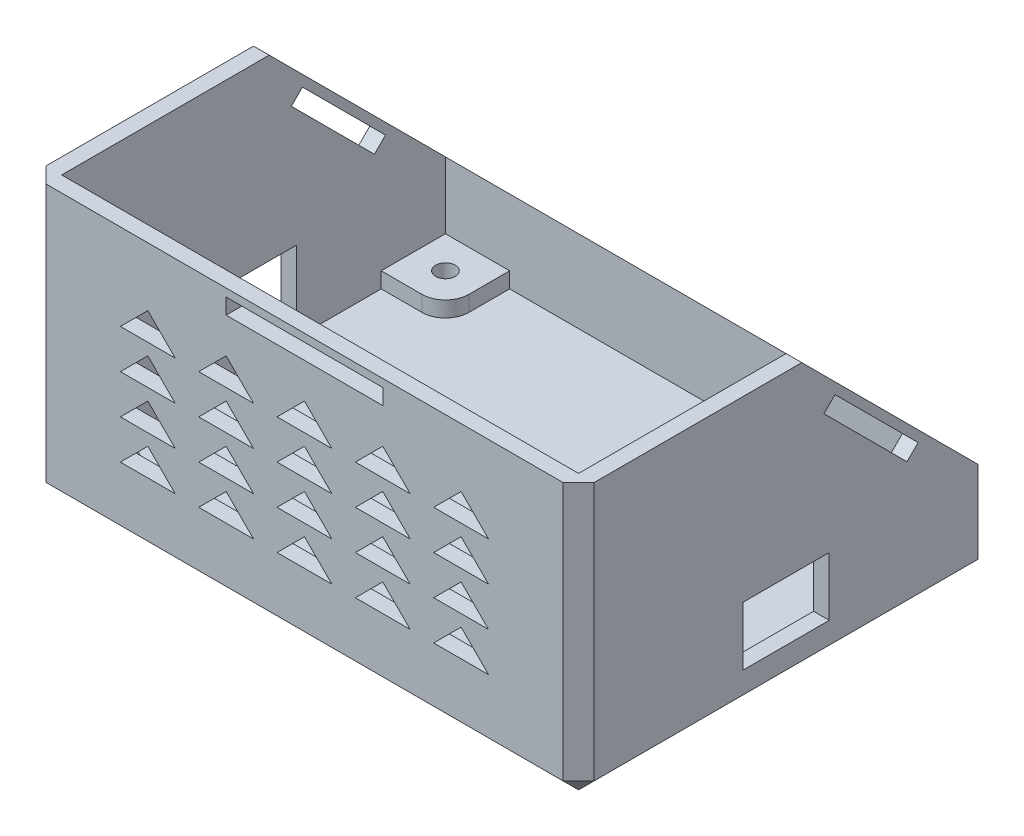
SolidWorks part; units mm, degrees
ref_plane "Front" through (0, 0, 0) normal (0, 0, 1) x (1, 0, 0)
ref_plane "Top" through (0, 0, 0) normal (0, 1, 0) x (1, 0, 0)
ref_plane "Right" through (0, 0, 0) normal (1, 0, 0) x (0, 0, -1)
sketch "Sketch1" plane through (0, 0, 0) normal (0, 1, 0) x (1, 0, 0)
  line L0 (-35, 26.5) -> (35, 26.5)
  line L1 (-33, -24.5) -> (33, -24.5)
  line L2 (-33, -24.5) -> (-33, 24.5)
  line L3 (-33, 24.5) -> (33, 24.5)
  line L4 (33, -24.5) -> (33, 24.5)
  line L5 (-33, -24.5) -> (33, 24.5) construction
  line L6 (-33, 24.5) -> (33, -24.5) construction
  line L7 (35, -26.5) -> (35, 26.5)
  line L8 (-35, -26.5) -> (35, -26.5)
  line L9 (-35, -26.5) -> (-35, 26.5)
  point P0 (0, 0)
  dimension "D1" = 49
  dimension "D2" = 66
  dimension "D3" = 2
extrude "Boss-Extrude1" add sketch "Sketch1" along normal blind 2 contours L1 L4 L3 L2 | L9 L8 L7 L0 L4 L1 L2 L3 region at (0, 0, -25.622) region at (0, 0, 0)
extrude "Boss-Extrude2" add sketch "Sketch1<3>" along normal blind 33 from surface starting at face at (0, 2, 0)
sketch "Sketch1<3>" plane through (0, 0, 0) normal (0, 1, 0) x (1, 0, 0) same geometry as "Sketch1"
chamfer "Chamfer1" distance 2 angle 45 8 edges at (0, 0, 26.5) (35, 17.5, 26.5) (35, 0, 0) (35, 17.5, -26.5) (0, 0, -26.5) (-35, 17.5, -26.5) (-35, 0, 0) (-35, 17.5, 26.5)
sketch "Sketch2" plane through (0, 2, 0) normal (0, 1, 0) x (1, 0, 0)
  line L0 (-33, 16.3) -> (-27.8, 16.3)
  line L1 (-33, 24.5) -> (-24.8, 24.5)
  line L2 (-33, 24.5) -> (-33, 16.3)
  line L3 (-33, 16.3) -> (-24.8, 16.3) construction
  line L4 (-24.8, 24.5) -> (-24.8, 16.3) construction
  line L5 (-24.8, 24.5) -> (-24.8, 19.3)
  line L7 (-28.9, -20.4) -> (28.9, -20.4) construction
  line L8 (-28.9, -20.4) -> (-28.9, 20.4) construction
  line L9 (-28.9, 20.4) -> (28.9, 20.4) construction
  line L10 (28.9, -20.4) -> (28.9, 20.4) construction
  line L11 (-28.9, -20.4) -> (28.9, 20.4) construction
  line L12 (-28.9, 20.4) -> (28.9, -20.4) construction
  circle A0 centre (-28.9, 20.4) radius 1.25
  arc A1 (-27.8, 16.3) -> (-24.8, 19.3) centre (-27.8, 19.3) ccw
  point P7 (0, 0)
  point P8 (-24.8, 20.4)
  point P10 (-28.9, 16.3)
  point P13 (-24.8, 16.3)
  dimension "D1" = 3
  dimension "D3" = 2.5
  dimension "D2" = 40.8
extrude "Boss-Extrude3" add sketch "Sketch2" along normal blind 2
mirror "Mirror1" about plane through (0, 0, 0) normal (0, 0, 1) of "Boss-Extrude3"
mirror "Mirror2" about plane through (0, 0, 0) normal (1, 0, 0) of "Boss-Extrude3", "Mirror1"
sketch "Sketch3" plane through (0, 0, 0) normal (0, -1, 0) x (1, 0, 0)
  line L0 (-30.1124, 22.5) -> (-27.6876, 22.5)
  line L1 (-27.6876, 22.5) -> (-26.4751, 20.4)
  line L2 (-26.4751, 20.4) -> (-27.6876, 18.3)
  line L3 (-27.6876, 18.3) -> (-30.1124, 18.3)
  line L4 (-30.1124, 18.3) -> (-31.3249, 20.4)
  line L5 (-31.3249, 20.4) -> (-30.1124, 22.5)
  circle A1 centre (-28.9, 20.4) radius 2.4249 construction
  dimension "D1" = 4.2
extrude "Cut-Extrude1" cut sketch "Sketch3" against normal blind 1.6
mirror "Mirror3" about plane through (0, 0, 0) normal (0, 0, 1) of "Cut-Extrude1"
mirror "Mirror4" about plane through (0, 0, 0) normal (1, 0, 0) of "Mirror3", "Cut-Extrude1"
sketch "Sketch4" plane through (0, 2, 0) normal (0, 1, 0) x (1, 0, 0)
  circle A0 centre (28.9, -20.4) radius 1.25
  circle A1 centre (28.9, 20.4) radius 1.25
  circle A2 centre (-28.9, 20.4) radius 1.25
  circle A3 centre (-28.9, -20.4) radius 1.25
  circle A4 centre (-28.9, -20.4) radius 1.25 construction
extrude "Cut-Extrude2" cut sketch "Sketch4" against normal through all both and the other way through all
sketch "Sketch7" plane through (35, 0, 0) normal (1, 0, 0) x (0, 0, -1)
  line L1 (-5.5, 12.25) -> (5.5, 12.25)
  line L2 (-5.5, 12.25) -> (-5.5, 4.75)
  line L3 (-5.5, 4.75) -> (5.5, 4.75)
  line L4 (5.5, 12.25) -> (5.5, 4.75)
  point P4 (0, 4.75)
  dimension "D1" = 11
  dimension "D2" = 7.5
  dimension "D3" = 0.75
extrude "Cut-Extrude5" cut sketch "Sketch7" against normal through all
sketch "Sketch5" plane through (0, 0, 24.5) normal (0, 0, -1) x (-1, 0, 0)
  line L0 (33, 35) -> (-33, 35) construction
  line L1 (-10, 34) -> (10, 34)
  line L2 (-10, 34) -> (-10, 32)
  line L3 (-10, 32) -> (10, 32)
  line L4 (10, 34) -> (10, 32)
  point P4 (0, 34)
  dimension "D1" = 2
  dimension "D2" = 1
  dimension "D3" = 20
extrude "Cut-Extrude3" cut sketch "Sketch5" against normal through all both and the other way through all
sketch "Sketch8" plane through (35, 0, 0) normal (1, 0, 0) x (0, 0, -1)
  line L0 (-4.5, 35) -> (-4.5, 24)
  line L1 (24.5, 35) -> (-24.5, 35) construction
  line L2 (-4.5, 24) -> (10.5, 24)
  line L3 (10.5, 24) -> (10.5, 12.5486)
  line L4 (10.5, 12.5486) -> (26.5, 12.5486)
  line L5 (26.5, 35) -> (26.5, 2) construction
  line L6 (-4.5, 35) -> (26.5, 35)
  line L7 (26.5, 35) -> (26.5, 12.5486)
  line L8 (-24.5, 35) -> (-24.5, 2) construction
  dimension "D1" = 20
  dimension "D2" = 15
  dimension "D3" = 11
  dimension "D4" = 11.4514
extrude "Cut-Extrude7" [suppressed] cut sketch "Sketch8" against normal through all and the other way through all
sketch "Sketch9" plane through (35, 0, 0) normal (1, 0, 0) x (0, 0, -1)
  line L0 (2, 35) -> (26.5, 10.5)
  line L1 (24.5, 35) -> (-24.5, 35) construction
  line L3 (2, 35) -> (26.5, 35)
  line L4 (26.5, 35) -> (26.5, 10.5)
  line L5 (26.5, 35) -> (26.5, 2) construction
  dimension "D1" = 24.5
  dimension "D3" = 45
extrude "Cut-Extrude8" cut sketch "Sketch9" against normal through all
sketch "Sketch6" plane through (-33, 0, 0) normal (1, 0, 0) x (0, 0, -1)
  line L1 (6.2426, 29.3431) -> (16.8492, 18.7365)
  line L2 (6.2426, 29.3431) -> (4.8284, 27.9289)
  line L3 (4.8284, 27.9289) -> (15.435, 17.3223)
  line L4 (16.8492, 18.7365) -> (15.435, 17.3223)
  line L6 (2, 35) -> (24.5, 12.5) construction
  dimension "D1" = 15
  dimension "D2" = 2
  dimension "D3" = 1
  dimension "D4" = 7
extrude "Cut-Extrude4" cut sketch "Sketch6" against normal through all both and the other way through all
sketch "Sketch10" plane through (0, 0, 26.5) normal (0, 0, 1) x (1, 0, 0)
  line L0 (-28.2743, 28) -> (0, 28) construction
  line L1 (-28.2743, 28) -> (-28.2743, 26)
  line L2 (0, 28) -> (0, 26)
  line L3 (-28.2743, 26) -> (0, 26) construction
  spline S0 degree 4 poles (-28.5449, 27.7323) (-28.4703, 27.8051) (-28.3096, 27.9634) (-28.0891, 28.1885) (-27.7474, 28.5166) (-27.4578, 28.7408) (-27.1833, 28.8969) (-26.9792, 28.9694) (-26.7891, 29.0025) (-26.6154, 29.0023) (-26.4253, 28.969) (-26.2191, 28.8938) (-25.9523, 28.7444) (-25.6444, 28.5016) (-25.3138, 28.185) (-24.9517, 27.815) (-24.6211, 27.4984) (-24.3132, 27.2556) (-24.0464, 27.1062) (-23.8402, 27.031) (-23.6501, 26.9977) (-23.4764, 26.9975) (-23.2866, 27.0302) (-23.0803, 27.105) (-22.8134, 27.2536) (-22.5033, 27.4977) (-22.2688, 27.7226) (-21.9845, 28.0067) (-21.7217, 28.2692) (-21.4842, 28.4974) (-21.176, 28.7415) (-20.9066, 28.8936) (-20.6955, 28.97) (-20.5054, 29.0024) (-20.3321, 29.0022) (-20.1418, 28.969) (-19.9305, 28.8918) (-19.6613, 28.7391) (-19.3545, 28.4954) (-19.0269, 28.181) (-18.6722, 27.819) (-18.3446, 27.5046) (-18.0378, 27.2609) (-17.7686, 27.1082) (-17.5574, 27.031) (-17.3671, 26.9978) (-17.1937, 26.9976) (-17.0037, 27.03) (-16.7926, 27.1064) (-16.5231, 27.2585) (-16.2149, 27.5026) (-15.8864, 27.8183) (-15.5296, 28.1817) (-15.2011, 28.4974) (-14.8929, 28.7415) (-14.6234, 28.8936) (-14.4123, 28.97) (-14.2222, 29.0024) (-14.0489, 29.0022) (-13.8586, 28.969) (-13.6473, 28.8918) (-13.3781, 28.7391) (-13.0713, 28.4954) (-12.7437, 28.181) (-12.389, 27.819) (-12.0614, 27.5046) (-11.7546, 27.2609) (-11.4855, 27.1082) (-11.2742, 27.031) (-11.0839, 26.9978) (-10.9105, 26.9976) (-10.7205, 27.03) (-10.5094, 27.1064) (-10.2399, 27.2585) (-9.9317, 27.5026) (-9.6032, 27.8183) (-9.2464, 28.1817) (-8.9179, 28.4974) (-8.6097, 28.7415) (-8.3402, 28.8936) (-8.1291, 28.97) (-7.9391, 29.0024) (-7.7657, 29.0022) (-7.5754, 28.969) (-7.3641, 28.8918) (-7.0949, 28.7391) (-6.7881, 28.4954) (-6.4605, 28.181) (-6.1059, 27.819) (-5.7782, 27.5046) (-5.4715, 27.2609) (-5.2023, 27.1082) (-4.991, 27.031) (-4.8007, 26.9978) (-4.6273, 26.9976) (-4.4373, 27.03) (-4.2262, 27.1064) (-3.9567, 27.2585) (-3.6485, 27.5026) (-3.32, 27.8183) (-2.9632, 28.1817) (-2.6347, 28.4974) (-2.3265, 28.7415) (-2.057, 28.8936) (-1.8459, 28.97) (-1.6559, 29.0024) (-1.4825, 29.0022) (-1.2922, 28.969) (-1.0809, 28.8918) (-0.8117, 28.7391) (-0.505, 28.4954) (-0.1773, 28.181) (0.1773, 27.819) (0.505, 27.5046) (0.8117, 27.2609) (1.0809, 27.1082) (1.2922, 27.031) (1.4825, 26.9978) (1.6559, 26.9976) (1.8459, 27.03) (2.057, 27.1064) (2.3265, 27.2585) (2.6347, 27.5026) (2.9632, 27.8183) (3.32, 28.1817) (3.6485, 28.4974) (3.9567, 28.7415) (4.2262, 28.8936) (4.4373, 28.97) (4.6273, 29.0024) (4.8007, 29.0022) (4.991, 28.969) (5.2023, 28.8918) (5.4715, 28.7391) (5.7782, 28.4954) (6.1059, 28.181) (6.4605, 27.819) (6.7881, 27.5046) (7.0949, 27.2609) (7.3641, 27.1082) (7.5754, 27.031) (7.7657, 26.9978) (7.9391, 26.9976) (8.1291, 27.03) (8.3402, 27.1064) (8.6097, 27.2585) (8.9179, 27.5026) (9.2464, 27.8183) (9.6032, 28.1817) (9.9317, 28.4974) (10.2399, 28.7415) (10.5094, 28.8936) (10.7205, 28.97) (10.9105, 29.0024) (11.0839, 29.0022) (11.2742, 28.969) (11.4855, 28.8918) (11.7546, 28.7391) (12.0614, 28.4954) (12.389, 28.181) (12.7437, 27.819) (13.0713, 27.5046) (13.3781, 27.2609) (13.6473, 27.1082) (13.8586, 27.031) (14.0489, 26.9978) (14.2222, 26.9976) (14.4123, 27.03) (14.6234, 27.1064) (14.8929, 27.2585) (15.2011, 27.5026) (15.4388, 27.731) (15.6535, 27.946) (16.1642, 28.4542) (16.5088, 28.7676) (17.0389, 29.0097) (17.5058, 29.0109) (17.9194, 28.8311) (18.2971, 28.5403) (18.7576, 28.0983) (19.2008, 27.6407) (19.6509, 27.2313) (20.1778, 26.9912) (20.6495, 26.9884) (21.1777, 27.222) (21.7191, 27.7123) (22.2515, 28.2756) (22.7935, 28.7698) (23.3211, 29.0093) (23.7925, 29.011) (24.2049, 28.829) (24.5827, 28.5381) (24.9536, 28.1828) (25.301, 27.8281) (25.5956, 27.5448) (25.8423, 27.3416) (26.0345, 27.2133) (26.1568, 27.1427) (26.2955, 27.0788) (26.4442, 27.0275) (26.5772, 27.0044) (26.7085, 26.9975) (26.8225, 27.0051) (26.946, 27.0242) (27.0781, 27.0666) (27.1806, 27.1097) (27.2449, 27.1424) (27.2764, 27.1598) knots 0 0 0 0 0 0.005919 0.014015 0.02211 0.02645 0.030317 0.033015 0.035714 0.038403 0.041092 0.044998 0.049324 0.057392 0.06546 0.073527 0.081595 0.085922 0.089827 0.092516 0.095205 0.097904 0.100602 0.104469 0.108809 0.116905 0.125 0.125 0.133332 0.141664 0.146479 0.150644 0.153498 0.156276 0.159039 0.161939 0.166084 0.170918 0.179209 0.1875 0.195791 0.204082 0.208916 0.213061 0.215961 0.218724 0.221502 0.224356 0.228521 0.233336 0.241668 0.25 0.258332 0.266664 0.271479 0.275644 0.278498 0.281276 0.284039 0.286939 0.291084 0.295918 0.304209 0.3125 0.320791 0.329082 0.333916 0.338061 0.340961 0.343724 0.346502 0.349356 0.353521 0.358336 0.366668 0.375 0.383332 0.391664 0.396479 0.400644 0.403498 0.406276 0.409039 0.411939 0.416084 0.420918 0.429209 0.4375 0.445791 0.454082 0.458916 0.463061 0.465961 0.468724 0.471502 0.474356 0.478521 0.483336 0.491668 0.5 0.508332 0.516664 0.521479 0.525644 0.528498 0.531276 0.534039 0.536939 0.541084 0.545918 0.554209 0.5625 0.570791 0.579082 0.583916 0.588061 0.590961 0.593724 0.596502 0.599356 0.603521 0.608336 0.616668 0.625 0.633332 0.641664 0.646479 0.650644 0.653498 0.656276 0.659039 0.661939 0.666084 0.670918 0.679209 0.6875 0.695791 0.704082 0.708916 0.713061 0.715961 0.718724 0.721502 0.724356 0.728521 0.733336 0.741668 0.75 0.758332 0.766664 0.771479 0.775644 0.778498 0.781276 0.784039 0.786939 0.791084 0.795918 0.804209 0.8125 0.820791 0.829082 0.833916 0.838061 0.840961 0.843724 0.846502 0.849356 0.853521 0.858336 0.866668 0.875 0.875 0.883858 0.888871 0.892047 0.895178 0.900187 0.904634 0.90908 0.917972 0.923045 0.926238 0.92937 0.934379 0.943272 0.952164 0.957237 0.96043 0.963561 0.968571 0.973017 0.977464 0.98191 0.986356 0.987624 0.988892 0.99016 0.991429 0.993025 0.994622 0.99482 0.996115 0.99741 0.998705 1 1 1 1 1 construction
  spline S1 degree 4 poles (-28.2743, 28) (-28.1869, 28.0875) (-28.0126, 28.2619) (-27.7474, 28.5166) (-27.4578, 28.7408) (-27.1833, 28.8969) (-26.9792, 28.9694) (-26.7891, 29.0025) (-26.6154, 29.0023) (-26.4253, 28.969) (-26.2191, 28.8938) (-25.9523, 28.7444) (-25.6444, 28.5016) (-25.3138, 28.185) (-24.9517, 27.815) (-24.6211, 27.4984) (-24.3132, 27.2556) (-24.0464, 27.1062) (-23.8402, 27.031) (-23.6501, 26.9977) (-23.4764, 26.9975) (-23.2866, 27.0302) (-23.0803, 27.105) (-22.8134, 27.2536) (-22.5033, 27.4977) (-22.2688, 27.7226) (-21.9845, 28.0067) (-21.7217, 28.2692) (-21.4842, 28.4974) (-21.176, 28.7415) (-20.9066, 28.8936) (-20.6955, 28.97) (-20.5054, 29.0024) (-20.3321, 29.0022) (-20.1418, 28.969) (-19.9305, 28.8918) (-19.6613, 28.7391) (-19.3545, 28.4954) (-19.0269, 28.181) (-18.6722, 27.819) (-18.3446, 27.5046) (-18.0378, 27.2609) (-17.7686, 27.1082) (-17.5574, 27.031) (-17.3671, 26.9978) (-17.1937, 26.9976) (-17.0037, 27.03) (-16.7926, 27.1064) (-16.5231, 27.2585) (-16.2149, 27.5026) (-15.8864, 27.8183) (-15.5296, 28.1817) (-15.2011, 28.4974) (-14.8929, 28.7415) (-14.6234, 28.8936) (-14.4123, 28.97) (-14.2222, 29.0024) (-14.0489, 29.0022) (-13.8586, 28.969) (-13.6473, 28.8918) (-13.3781, 28.7391) (-13.0713, 28.4954) (-12.7437, 28.181) (-12.389, 27.819) (-12.0614, 27.5046) (-11.7546, 27.2609) (-11.4855, 27.1082) (-11.2742, 27.031) (-11.0839, 26.9978) (-10.9105, 26.9976) (-10.7205, 27.03) (-10.5094, 27.1064) (-10.2399, 27.2585) (-9.9317, 27.5026) (-9.6032, 27.8183) (-9.2464, 28.1817) (-8.9179, 28.4974) (-8.6097, 28.7415) (-8.3402, 28.8936) (-8.1291, 28.97) (-7.9391, 29.0024) (-7.7657, 29.0022) (-7.5754, 28.969) (-7.3641, 28.8918) (-7.0949, 28.7391) (-6.7881, 28.4954) (-6.4605, 28.181) (-6.1059, 27.819) (-5.7782, 27.5046) (-5.4715, 27.2609) (-5.2023, 27.1082) (-4.991, 27.031) (-4.8007, 26.9978) (-4.6273, 26.9976) (-4.4373, 27.03) (-4.2262, 27.1064) (-3.9567, 27.2585) (-3.6485, 27.5026) (-3.32, 27.8183) (-2.9632, 28.1817) (-2.6347, 28.4974) (-2.3265, 28.7415) (-2.057, 28.8936) (-1.8459, 28.97) (-1.6559, 29.0024) (-1.4825, 29.0022) (-1.2922, 28.969) (-1.0809, 28.8918) (-0.8117, 28.7391) (-0.505, 28.4954) (-0.2688, 28.2688) (-0.0896, 28.0896) (0, 28) knots 0.005919 0.005919 0.005919 0.005919 0.005919 0.014015 0.02211 0.02645 0.030317 0.033015 0.035714 0.038403 0.041092 0.044998 0.049324 0.057392 0.06546 0.073527 0.081595 0.085922 0.089827 0.092516 0.095205 0.097904 0.100602 0.104469 0.108809 0.116905 0.125 0.125 0.133332 0.141664 0.146479 0.150644 0.153498 0.156276 0.159039 0.161939 0.166084 0.170918 0.179209 0.1875 0.195791 0.204082 0.208916 0.213061 0.215961 0.218724 0.221502 0.224356 0.228521 0.233336 0.241668 0.25 0.258332 0.266664 0.271479 0.275644 0.278498 0.281276 0.284039 0.286939 0.291084 0.295918 0.304209 0.3125 0.320791 0.329082 0.333916 0.338061 0.340961 0.343724 0.346502 0.349356 0.353521 0.358336 0.366668 0.375 0.383332 0.391664 0.396479 0.400644 0.403498 0.406276 0.409039 0.411939 0.416084 0.420918 0.429209 0.4375 0.445791 0.454082 0.458916 0.463061 0.465961 0.468724 0.471502 0.474356 0.478521 0.483336 0.491668 0.5 0.508332 0.516664 0.521479 0.525644 0.528498 0.531276 0.534039 0.536939 0.541084 0.545918 0.554209 0.5625 0.5625 0.5625 0.5625 0.5625
  spline S2 degree 4 poles (-28.5449, 25.7323) (-28.4703, 25.8051) (-28.3096, 25.9634) (-28.0891, 26.1885) (-27.7474, 26.5166) (-27.4578, 26.7408) (-27.1833, 26.8969) (-26.9792, 26.9694) (-26.7891, 27.0025) (-26.6154, 27.0023) (-26.4253, 26.969) (-26.2191, 26.8938) (-25.9523, 26.7444) (-25.6444, 26.5016) (-25.3138, 26.185) (-24.9517, 25.815) (-24.6211, 25.4984) (-24.3132, 25.2556) (-24.0464, 25.1062) (-23.8402, 25.031) (-23.6501, 24.9977) (-23.4764, 24.9975) (-23.2866, 25.0302) (-23.0803, 25.105) (-22.8134, 25.2536) (-22.5033, 25.4977) (-22.2688, 25.7226) (-21.9845, 26.0067) (-21.7217, 26.2692) (-21.4842, 26.4974) (-21.176, 26.7415) (-20.9066, 26.8936) (-20.6955, 26.97) (-20.5054, 27.0024) (-20.3321, 27.0022) (-20.1418, 26.969) (-19.9305, 26.8918) (-19.6613, 26.7391) (-19.3545, 26.4954) (-19.0269, 26.181) (-18.6722, 25.819) (-18.3446, 25.5046) (-18.0378, 25.2609) (-17.7686, 25.1082) (-17.5574, 25.031) (-17.3671, 24.9978) (-17.1937, 24.9976) (-17.0037, 25.03) (-16.7926, 25.1064) (-16.5231, 25.2585) (-16.2149, 25.5026) (-15.8864, 25.8183) (-15.5296, 26.1817) (-15.2011, 26.4974) (-14.8929, 26.7415) (-14.6234, 26.8936) (-14.4123, 26.97) (-14.2222, 27.0024) (-14.0489, 27.0022) (-13.8586, 26.969) (-13.6473, 26.8918) (-13.3781, 26.7391) (-13.0713, 26.4954) (-12.7437, 26.181) (-12.389, 25.819) (-12.0614, 25.5046) (-11.7546, 25.2609) (-11.4855, 25.1082) (-11.2742, 25.031) (-11.0839, 24.9978) (-10.9105, 24.9976) (-10.7205, 25.03) (-10.5094, 25.1064) (-10.2399, 25.2585) (-9.9317, 25.5026) (-9.6032, 25.8183) (-9.2464, 26.1817) (-8.9179, 26.4974) (-8.6097, 26.7415) (-8.3402, 26.8936) (-8.1291, 26.97) (-7.9391, 27.0024) (-7.7657, 27.0022) (-7.5754, 26.969) (-7.3641, 26.8918) (-7.0949, 26.7391) (-6.7881, 26.4954) (-6.4605, 26.181) (-6.1059, 25.819) (-5.7782, 25.5046) (-5.4715, 25.2609) (-5.2023, 25.1082) (-4.991, 25.031) (-4.8007, 24.9978) (-4.6273, 24.9976) (-4.4373, 25.03) (-4.2262, 25.1064) (-3.9567, 25.2585) (-3.6485, 25.5026) (-3.32, 25.8183) (-2.9632, 26.1817) (-2.6347, 26.4974) (-2.3265, 26.7415) (-2.057, 26.8936) (-1.8459, 26.97) (-1.6559, 27.0024) (-1.4825, 27.0022) (-1.2922, 26.969) (-1.0809, 26.8918) (-0.8117, 26.7391) (-0.505, 26.4954) (-0.1773, 26.181) (0.1773, 25.819) (0.505, 25.5046) (0.8117, 25.2609) (1.0809, 25.1082) (1.2922, 25.031) (1.4825, 24.9978) (1.6559, 24.9976) (1.8459, 25.03) (2.057, 25.1064) (2.3265, 25.2585) (2.6347, 25.5026) (2.9632, 25.8183) (3.32, 26.1817) (3.6485, 26.4974) (3.9567, 26.7415) (4.2262, 26.8936) (4.4373, 26.97) (4.6273, 27.0024) (4.8007, 27.0022) (4.991, 26.969) (5.2023, 26.8918) (5.4715, 26.7391) (5.7782, 26.4954) (6.1059, 26.181) (6.4605, 25.819) (6.7881, 25.5046) (7.0949, 25.2609) (7.3641, 25.1082) (7.5754, 25.031) (7.7657, 24.9978) (7.9391, 24.9976) (8.1291, 25.03) (8.3402, 25.1064) (8.6097, 25.2585) (8.9179, 25.5026) (9.2464, 25.8183) (9.6032, 26.1817) (9.9317, 26.4974) (10.2399, 26.7415) (10.5094, 26.8936) (10.7205, 26.97) (10.9105, 27.0024) (11.0839, 27.0022) (11.2742, 26.969) (11.4855, 26.8918) (11.7546, 26.7391) (12.0614, 26.4954) (12.389, 26.181) (12.7437, 25.819) (13.0713, 25.5046) (13.3781, 25.2609) (13.6473, 25.1082) (13.8586, 25.031) (14.0489, 24.9978) (14.2222, 24.9976) (14.4123, 25.03) (14.6234, 25.1064) (14.8929, 25.2585) (15.2011, 25.5026) (15.4388, 25.731) (15.6535, 25.946) (16.1642, 26.4542) (16.5088, 26.7676) (17.0389, 27.0097) (17.5058, 27.0109) (17.9194, 26.8311) (18.2971, 26.5403) (18.7576, 26.0983) (19.2008, 25.6407) (19.6509, 25.2313) (20.1778, 24.9912) (20.6495, 24.9884) (21.1777, 25.222) (21.7191, 25.7123) (22.2515, 26.2756) (22.7935, 26.7698) (23.3211, 27.0093) (23.7925, 27.011) (24.2049, 26.829) (24.5827, 26.5381) (24.9536, 26.1828) (25.301, 25.8281) (25.5956, 25.5448) (25.8423, 25.3416) (26.0345, 25.2133) (26.1568, 25.1427) (26.2955, 25.0788) (26.4442, 25.0275) (26.5772, 25.0044) (26.7085, 24.9975) (26.8225, 25.0051) (26.946, 25.0242) (27.0781, 25.0666) (27.1806, 25.1097) (27.2449, 25.1424) (27.2764, 25.1598) knots 0 0 0 0 0 0.005919 0.014015 0.02211 0.02645 0.030317 0.033015 0.035714 0.038403 0.041092 0.044998 0.049324 0.057392 0.06546 0.073527 0.081595 0.085922 0.089827 0.092516 0.095205 0.097904 0.100602 0.104469 0.108809 0.116905 0.125 0.125 0.133332 0.141664 0.146479 0.150644 0.153498 0.156276 0.159039 0.161939 0.166084 0.170918 0.179209 0.1875 0.195791 0.204082 0.208916 0.213061 0.215961 0.218724 0.221502 0.224356 0.228521 0.233336 0.241668 0.25 0.258332 0.266664 0.271479 0.275644 0.278498 0.281276 0.284039 0.286939 0.291084 0.295918 0.304209 0.3125 0.320791 0.329082 0.333916 0.338061 0.340961 0.343724 0.346502 0.349356 0.353521 0.358336 0.366668 0.375 0.383332 0.391664 0.396479 0.400644 0.403498 0.406276 0.409039 0.411939 0.416084 0.420918 0.429209 0.4375 0.445791 0.454082 0.458916 0.463061 0.465961 0.468724 0.471502 0.474356 0.478521 0.483336 0.491668 0.5 0.508332 0.516664 0.521479 0.525644 0.528498 0.531276 0.534039 0.536939 0.541084 0.545918 0.554209 0.5625 0.570791 0.579082 0.583916 0.588061 0.590961 0.593724 0.596502 0.599356 0.603521 0.608336 0.616668 0.625 0.633332 0.641664 0.646479 0.650644 0.653498 0.656276 0.659039 0.661939 0.666084 0.670918 0.679209 0.6875 0.695791 0.704082 0.708916 0.713061 0.715961 0.718724 0.721502 0.724356 0.728521 0.733336 0.741668 0.75 0.758332 0.766664 0.771479 0.775644 0.778498 0.781276 0.784039 0.786939 0.791084 0.795918 0.804209 0.8125 0.820791 0.829082 0.833916 0.838061 0.840961 0.843724 0.846502 0.849356 0.853521 0.858336 0.866668 0.875 0.875 0.883858 0.888871 0.892047 0.895178 0.900187 0.904634 0.90908 0.917972 0.923045 0.926238 0.92937 0.934379 0.943272 0.952164 0.957237 0.96043 0.963561 0.968571 0.973017 0.977464 0.98191 0.986356 0.987624 0.988892 0.99016 0.991429 0.993025 0.994622 0.99482 0.996115 0.99741 0.998705 1 1 1 1 1 construction
  spline S3 degree 4 poles (-28.2743, 26) (-28.1869, 26.0875) (-28.0126, 26.2619) (-27.7474, 26.5166) (-27.4578, 26.7408) (-27.1833, 26.8969) (-26.9792, 26.9694) (-26.7891, 27.0025) (-26.6154, 27.0023) (-26.4253, 26.969) (-26.2191, 26.8938) (-25.9523, 26.7444) (-25.6444, 26.5016) (-25.3138, 26.185) (-24.9517, 25.815) (-24.6211, 25.4984) (-24.3132, 25.2556) (-24.0464, 25.1062) (-23.8402, 25.031) (-23.6501, 24.9977) (-23.4764, 24.9975) (-23.2866, 25.0302) (-23.0803, 25.105) (-22.8134, 25.2536) (-22.5033, 25.4977) (-22.2688, 25.7226) (-21.9845, 26.0067) (-21.7217, 26.2692) (-21.4842, 26.4974) (-21.176, 26.7415) (-20.9066, 26.8936) (-20.6955, 26.97) (-20.5054, 27.0024) (-20.3321, 27.0022) (-20.1418, 26.969) (-19.9305, 26.8918) (-19.6613, 26.7391) (-19.3545, 26.4954) (-19.0269, 26.181) (-18.6722, 25.819) (-18.3446, 25.5046) (-18.0378, 25.2609) (-17.7686, 25.1082) (-17.5574, 25.031) (-17.3671, 24.9978) (-17.1937, 24.9976) (-17.0037, 25.03) (-16.7926, 25.1064) (-16.5231, 25.2585) (-16.2149, 25.5026) (-15.8864, 25.8183) (-15.5296, 26.1817) (-15.2011, 26.4974) (-14.8929, 26.7415) (-14.6234, 26.8936) (-14.4123, 26.97) (-14.2222, 27.0024) (-14.0489, 27.0022) (-13.8586, 26.969) (-13.6473, 26.8918) (-13.3781, 26.7391) (-13.0713, 26.4954) (-12.7437, 26.181) (-12.389, 25.819) (-12.0614, 25.5046) (-11.7546, 25.2609) (-11.4855, 25.1082) (-11.2742, 25.031) (-11.0839, 24.9978) (-10.9105, 24.9976) (-10.7205, 25.03) (-10.5094, 25.1064) (-10.2399, 25.2585) (-9.9317, 25.5026) (-9.6032, 25.8183) (-9.2464, 26.1817) (-8.9179, 26.4974) (-8.6097, 26.7415) (-8.3402, 26.8936) (-8.1291, 26.97) (-7.9391, 27.0024) (-7.7657, 27.0022) (-7.5754, 26.969) (-7.3641, 26.8918) (-7.0949, 26.7391) (-6.7881, 26.4954) (-6.4605, 26.181) (-6.1059, 25.819) (-5.7782, 25.5046) (-5.4715, 25.2609) (-5.2023, 25.1082) (-4.991, 25.031) (-4.8007, 24.9978) (-4.6273, 24.9976) (-4.4373, 25.03) (-4.2262, 25.1064) (-3.9567, 25.2585) (-3.6485, 25.5026) (-3.32, 25.8183) (-2.9632, 26.1817) (-2.6347, 26.4974) (-2.3265, 26.7415) (-2.057, 26.8936) (-1.8459, 26.97) (-1.6559, 27.0024) (-1.4825, 27.0022) (-1.2922, 26.969) (-1.0809, 26.8918) (-0.8117, 26.7391) (-0.505, 26.4954) (-0.2688, 26.2688) (-0.0896, 26.0896) (0, 26) knots 0.005919 0.005919 0.005919 0.005919 0.005919 0.014015 0.02211 0.02645 0.030317 0.033015 0.035714 0.038403 0.041092 0.044998 0.049324 0.057392 0.06546 0.073527 0.081595 0.085922 0.089827 0.092516 0.095205 0.097904 0.100602 0.104469 0.108809 0.116905 0.125 0.125 0.133332 0.141664 0.146479 0.150644 0.153498 0.156276 0.159039 0.161939 0.166084 0.170918 0.179209 0.1875 0.195791 0.204082 0.208916 0.213061 0.215961 0.218724 0.221502 0.224356 0.228521 0.233336 0.241668 0.25 0.258332 0.266664 0.271479 0.275644 0.278498 0.281276 0.284039 0.286939 0.291084 0.295918 0.304209 0.3125 0.320791 0.329082 0.333916 0.338061 0.340961 0.343724 0.346502 0.349356 0.353521 0.358336 0.366668 0.375 0.383332 0.391664 0.396479 0.400644 0.403498 0.406276 0.409039 0.411939 0.416084 0.420918 0.429209 0.4375 0.445791 0.454082 0.458916 0.463061 0.465961 0.468724 0.471502 0.474356 0.478521 0.483336 0.491668 0.5 0.508332 0.516664 0.521479 0.525644 0.528498 0.531276 0.534039 0.536939 0.541084 0.545918 0.554209 0.5625 0.5625 0.5625 0.5625 0.5625
  dimension "D1" = 28
  dimension "D2" = 28.2743
  dimension "D3" = 2
sketch "Sketch11" plane through (0, 0, 26.5) normal (0, 0, 1) x (1, 0, 0)
  line L0 (0, 0) -> (0, 35) construction
  line L1 (33, 35) -> (-33, 35) construction
  line L2 (0, 27.5) -> (-3.5, 24)
  line L3 (-3.5, 24) -> (3.5, 24)
  line L4 (3.5, 24) -> (0, 27.5)
  line L17 (33, 0) -> (-33, 0) construction
  dimension "D1" = 90
  dimension "D2" = 7
  dimension "D3" = 24
extrude "Cut-Extrude9" cut sketch "Sketch11" against normal up to next
pattern_linear "LPattern2" count 3 spacing 10 along (1, 0, 0) count 3 spacing 10 along (-1, 0, 0) of "Cut-Extrude9" pattern seed only yes
pattern_linear "LPattern3" count 4 spacing 5 along (0, -1, 0) of "LPattern2", "Cut-Extrude9"
